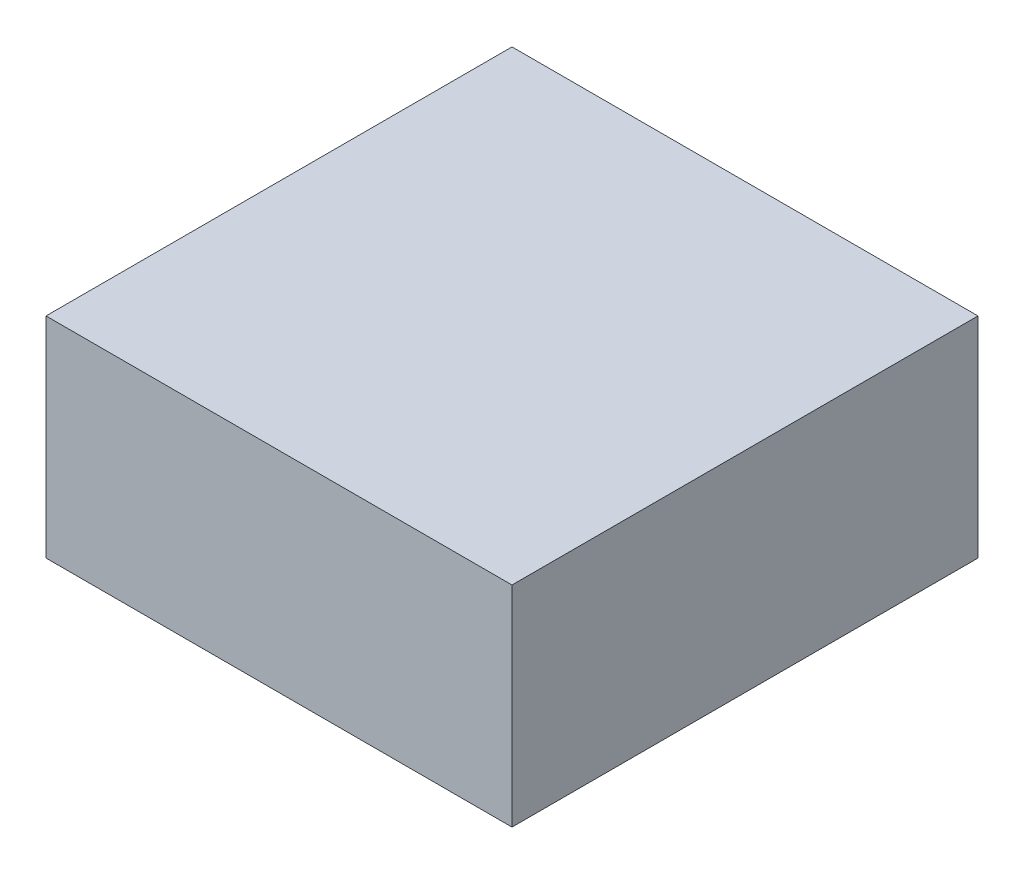
SolidWorks part; units mm, degrees
ref_plane "Front Plane" through (0, 0, 0) normal (0, 0, 1) x (1, 0, 0)
ref_plane "Top Plane" through (0, 0, 0) normal (0, 1, 0) x (1, 0, 0)
ref_plane "Right Plane" through (0, 0, 0) normal (1, 0, 0) x (0, 0, -1)
sketch "Sketch1" plane through (0, 0, 0) normal (0, 0, 1) x (1, 0, 0)
  line L1 (-10, -5) -> (10, -5)
  line L2 (-10, -5) -> (-10, 4)
  line L3 (-10, 4) -> (10, 4)
  line L4 (10, -5) -> (10, 4)
  line L5 (-5, 0) -> (5, 0) construction
  circle A0 centre (-5, 0) radius 2
  circle A1 centre (5, 0) radius 2
  point P10 (0, 4)
  point P11 (0, 0)
  dimension "D4" = 4
  dimension "D1" = 9
  dimension "D3" = 20
  dimension "D5" = 10
  dimension "D6" = 4
extrude "Boss-Extrude1" add sketch "Sketch1" along normal blind 20 contours L2 L3 L4 L1
extrude "Cut-Extrude2" cut sketch "Sketch1<10>" along normal blind 10 contours A1 | A0 region at (-5, 0, 0) region at (5, 0, 0)
sketch "Sketch1<10>" plane through (0, 0, 0) normal (0, 0, 1) x (1, 0, 0) same geometry as "Sketch1"
sketch "Sketch2" plane through (0, 0, 0) normal (0, 0, 1) x (1, 0, 0)
  circle A0 centre (-5, 0) radius 2.75
  circle A1 centre (5, 0) radius 2.75
  point P5 (0, 0)
  point P6 (-5.6274, 12.2898)
  point P7 (9.3039, 9.1709)
  point P12 (0, 0)
  dimension "D1" = 5.5
extrude "Cut-Extrude1" cut sketch "Sketch2" along normal blind 7
